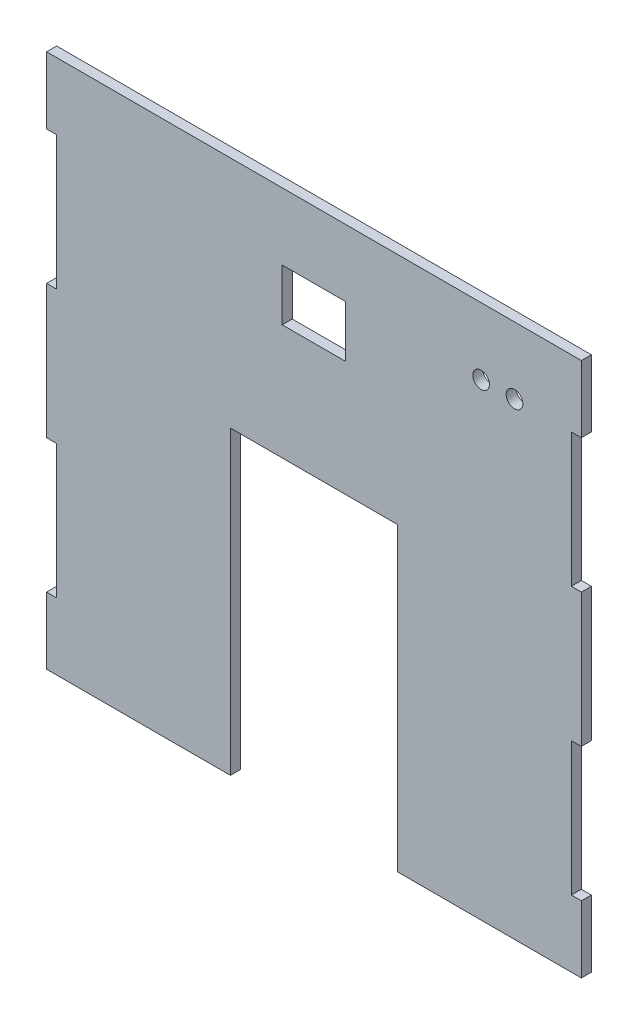
SolidWorks part; units mm, degrees
ref_plane "Front Plane" through (0, 0, 0) normal (0, 0, 1) x (1, 0, 0)
ref_plane "Top Plane" through (0, 0, 0) normal (0, 1, 0) x (1, 0, 0)
ref_plane "Right Plane" through (0, 0, 0) normal (1, 0, 0) x (0, 0, -1)
sketch "Sketch1" plane through (0, 0, 0) normal (0, 0, 1) x (1, 0, 0)
  line L0 (0, 10) -> (0, 80) construction
  line L1 (-80, 80) -> (80, 80)
  line L2 (-80, 80) -> (-80, -80)
  line L3 (-80, -80) -> (80, -80)
  line L4 (80, 80) -> (80, -80)
  line L5 (-80, 80) -> (80, -80) construction
  line L6 (-80, -80) -> (80, 80) construction
  line L7 (-25, -80) -> (25, -80)
  line L8 (-25, -80) -> (-25, 10)
  line L9 (-25, 10) -> (25, 10)
  line L10 (25, -80) -> (25, 10)
  line L11 (80, 60) -> (-80, 60) construction
  line L12 (0, 80) -> (0, 60) construction
  line L13 (-9.5, 60) -> (9.5, 60)
  line L14 (-9.5, 60) -> (-9.5, 44.5)
  line L15 (-9.5, 44.5) -> (9.5, 44.5)
  line L16 (9.5, 60) -> (9.5, 44.5)
  circle A0 centre (50, 60) radius 2.5
  circle A1 centre (60, 60) radius 2.5
  point P0 (0, 0)
  dimension "D6" = 5
  dimension "D1" = 160
  dimension "D2" = 160
  dimension "D3" = 90
  dimension "D4" = 50
  dimension "D5" = 20
  dimension "D7" = 10
  dimension "D8" = 20
  dimension "D9" = 19
  dimension "D10" = 15.5
extrude "Boss-Extrude1" add sketch "Sketch1" along normal blind 3 contours L10 L3 L4 L1 L2 L8 L9 A1 A0 L13 L16 L15 L14 region at (0, 77.7373, 0)
sketch "Sketch2" plane through (0, 0, 3) normal (0, 0, 1) x (1, 0, 0)
  line L0 (-80, -60) -> (-77, -60)
  line L1 (-80, 80) -> (-80, -80) construction
  line L2 (-77, -60) -> (-77, -20)
  line L3 (-77, -20) -> (-80, -20)
  line L4 (-80, -20) -> (-80, 20)
  line L5 (-80, 20) -> (-77, 20)
  line L6 (-77, 20) -> (-77, 60)
  line L7 (-77, 60) -> (-80, 60)
  line L8 (-80, 60) -> (-80, -60)
  line L9 (-77, 20) -> (-77, -20) construction
  line L10 (-77, 0) -> (80, 0) construction
  line L11 (80, 80) -> (80, -80) construction
  line L12 (80, 60) -> (77, 60)
  line L13 (77, 60) -> (77, 20)
  line L14 (77, 20) -> (80, 20)
  line L15 (80, 20) -> (80, -20)
  line L16 (80, -20) -> (77, -20)
  line L17 (77, -20) -> (77, -60)
  line L18 (77, -60) -> (80, -60)
  line L19 (80, -60) -> (80, 60)
  line L20 (77, 20) -> (77, -20) construction
  line L21 (77, 0) -> (-80, 0) construction
  line M21 (80, -80) -> (80, 80)
  line M23 (-80, 80) -> (-80, -80)
  dimension "D1" = 40
  dimension "D2" = 40
  dimension "D3" = 3
  dimension "D4" = 40
  dimension "D5" = 3
  dimension "D6" = 40
extrude "Cut-Extrude1" cut sketch "Sketch2" against normal through all contours L6 L7 L5 M23 | L2 L3 L0 M23 | L17 L18 L16 M21 | L13 L14 L12 M21 | L19 L12 L13 L14 L15 L16 L17 L18 region at (-78.5, -40, 3) region at (-78.5, 40, 3) region at (78.5, 40, 3) region at (78.5, -40, 3)
